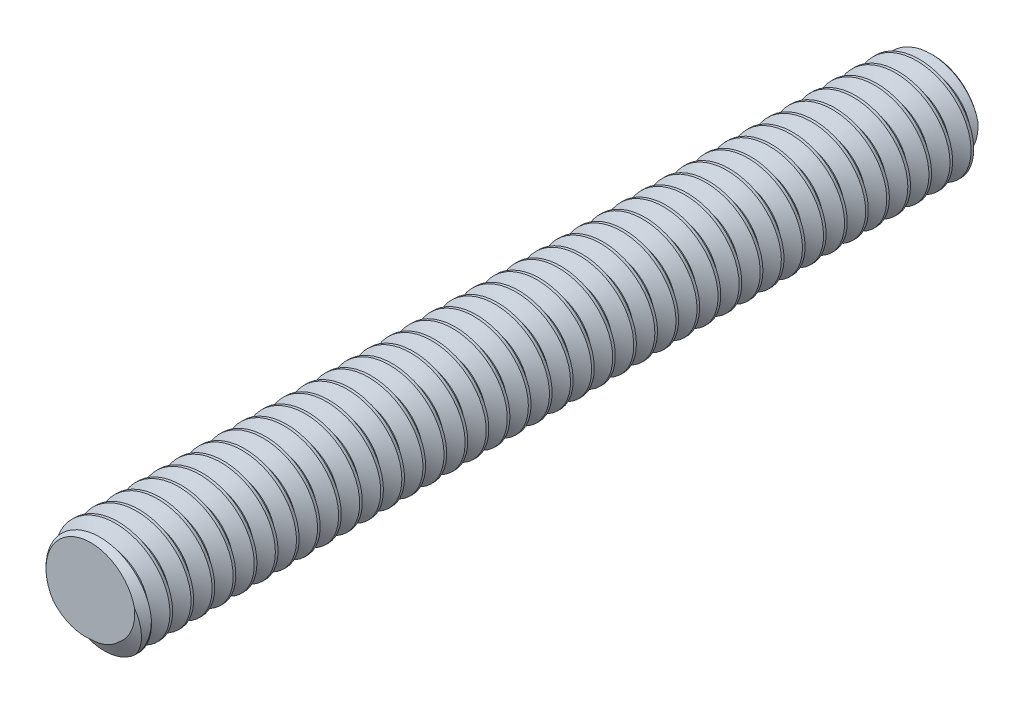
SolidWorks part; units mm, degrees
note: '?' marks a value the reader was unsure of.
ref_plane "Front Plane" through (0, 0, 0) normal (0, 0, 1) x (1, 0, 0)
ref_plane "Top Plane" through (0, 0, 0) normal (0, 1, 0) x (1, 0, 0)
ref_plane "Right Plane" through (0, 0, 0) normal (1, 0, 0) x (0, 0, -1)
sketch "Sketch1" plane through (0, 0, 0) normal (1, 0, 0) x (0, 0, -1)
  line L0 (25.4, 0) -> (-25.4, 0) construction
  line L1 (-25.4, -3.175) -> (-25.4, 3.175) construction
  line L2 (-25.4, 3.175) -> (-26.67, 3.175) construction
  line L3 (25.4, 3.175) -> (25.4, -3.175) construction
  point P3 (25.4, 3.175)
  point P4 (0, 0)
  point P7 (-25.4, 0)
  point P8 (-22.225, -3.175)
  point P10 (20.32, 0)
  point P11 (-20.32, 0)
  point P12 (-15.875, 3.175)
  point P13 (25.4, 0)
  point P15 (15.875, 3.175)
  dimension "OD" = 6.35
  dimension "Pitch" = 1.27
  dimension "Length" = 50.8
  dimension "D1" = 3.175
  dimension "D2" = 5.08
  dimension "D3" = 5.08
  dimension "D4" = 9.525
  dimension "D5" = 9.525
sketch "Sketch2" plane through (0, 0, 0) normal (0, 0, 1) x (1, 0, 0)
  line L0 (0, -3.175) -> (0, 3.175) construction
  line L1 (-3.175, 0) -> (3.175, 0) construction
  circle A0 centre (0, 0) radius 3.175
extrude "Boss-Extrude1" add sketch "Sketch2" along normal up to vertex (25.4 mm away) and the other way up to vertex (25.4 mm away) up to point (0, 0, 25.4) other way up to point (0, 0, -25.4)
chamfer "Chamfer1" distance 0.4762 angle 45 2 edges at (3.175, 0, -25.4) (3.175, 0, 25.4)
ref_axis "Center Axis 1" through (0, 0, -25.4) along (0, 0, 1)?
sketch "Sketch13" plane through (0, 0, 25.4) normal (0, 0, 1) x (1, 0, 0)
  circle A0 centre (0, 0) radius 3.175
curve "Helix/Spiral2" pitch 1.27 height 63.5 turns 50
sketch "Sketch23" plane through (0, 0, 0) normal (1, 0, 0) x (0, 0, -1)
  line L0 (-26.5906, 3.3125) -> (-25.3206, 3.3125) construction
  line L1 (-25.3206, 3.3125) -> (-25.9556, 2.2126) construction
  line L2 (-25.9556, 2.2126) -> (-26.5906, 3.3125) construction
  line L3 (-25.9556, 3.3125) -> (-25.9556, 3.175) construction
  line L4 (-25.9556, 3.175) -> (-25.9556, 2.3501) construction
  line L5 (-25.9556, 2.3501) -> (-25.9556, 2.2126) construction
  line L6 (-26.5112, 3.175) -> (-25.4, 3.175) construction
  line L8 (-25.8762, 2.3501) -> (-26.035, 2.3501) construction
  line L10 (-26.5509, 3.2437) -> (-25.3603, 3.2437) construction
  line L11 (-25.8762, 2.3501) -> (-26.035, 2.3501)
  line L12 (-26.035, 2.3501) -> (-26.5509, 3.2437)
  line L13 (-26.5509, 3.2437) -> (-25.3603, 3.2437)
  line L14 (-25.3603, 3.2437) -> (-25.8762, 2.3501)
  point P9 (-25.9556, 3.175)
  point P13 (-25.9556, 2.3501)
  point P14 (-25.9556, 3.2437)
  point P15 (-25.9556, 3.2437)
  dimension "D1" = 1.27
  dimension "D2" = 0.1588
sweep "Cut-Sweep1" cut profiles "Sketch23" path "Helix/Spiral2"
equation "\"D1@Chamfer1\"=\"OD@Sketch1\"*.075"
equation "\"D1@Sketch1\"=\"Pitch@Sketch1\"*2.5"
equation "\"D2@Sketch1\"=\"Pitch@Sketch1\"*4"
equation "\"D3@Sketch1\"=\"D2@Sketch1\""
equation "\"D4@Helix/Spiral2\"=\"Pitch@Sketch1\""
equation "\"D3@Helix/Spiral2\"=\"Length@Sketch1\"*1.25"
equation "\"D4@Sketch1\"=\"OD@Sketch1\"*1.5"
equation "\"D5@Sketch1\"=\"OD@Sketch1\"*1.5"
equation "\"D1@Sketch23\"=\"Pitch@Sketch1\""
equation "\"D2@Sketch23\"=\"D1@Sketch23\"/8"
